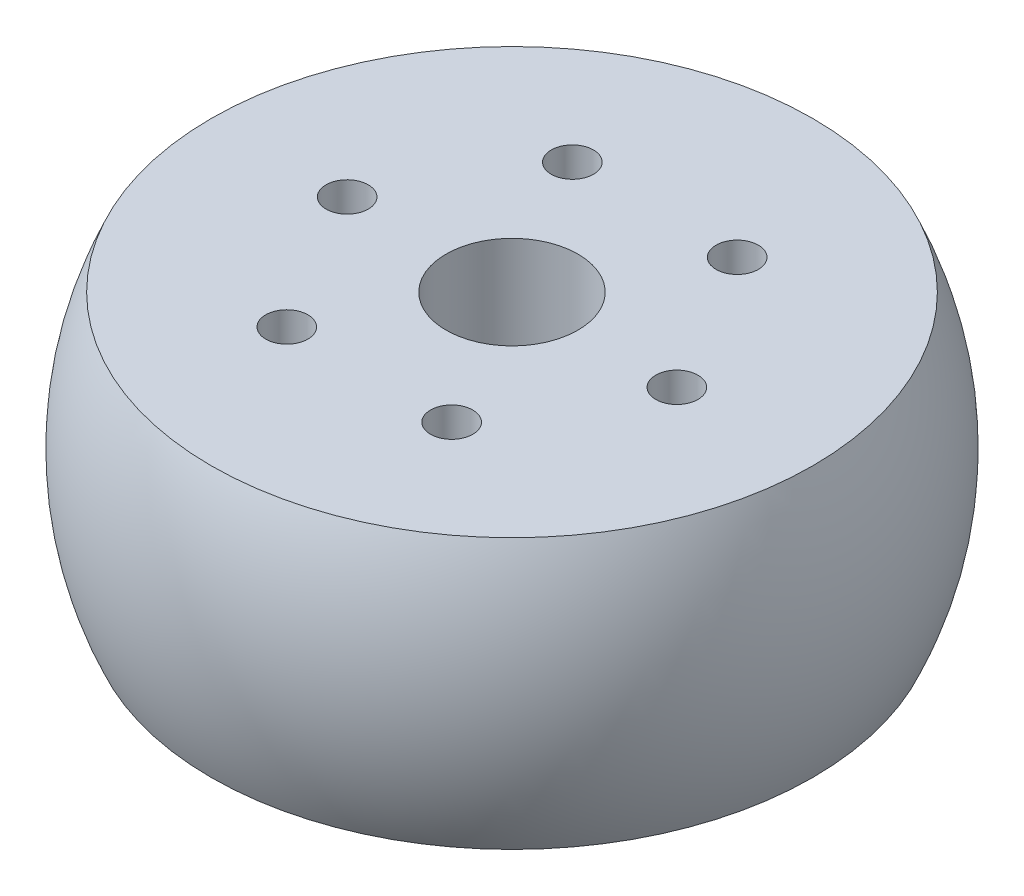
SolidWorks part; units mm, degrees
ref_plane "Front Plane" through (0, 0, 0) normal (0, 0, 1) x (1, 0, 0)
ref_plane "Top Plane" through (0, 0, 0) normal (0, 1, 0) x (1, 0, 0)
ref_plane "Right Plane" through (0, 0, 0) normal (1, 0, 0) x (0, 0, -1)
sketch "Sketch1" plane through (0, 0, 0) normal (1, 0, 0) x (0, 0, -1)
  line L0 (0, -6.5) -> (0, 6.5) construction
  line L1 (3.175, 6.5) -> (14.4833, 6.5)
  line L2 (3.175, 6.5) -> (3.175, -6.5)
  line L3 (3.175, -6.5) -> (14.4833, -6.5)
  line L4 (15.875, 0) -> (0, 0) construction
  circle A0 centre (0, 0) radius 15.875 construction
  arc A1 (14.4833, 6.5) -> (14.4833, -6.5) centre (0, 0) cw
  point P4 (0, 0)
  dimension "D1" = 6.35
  dimension "D2" = 13
  dimension "D3" = 15.875
revolve "Revolve1" add sketch "Sketch1" angle 360 about L0
sketch "Sketch3" plane through (0, 0, 0) normal (0, 1, 0) x (1, 0, 0)
  line L0 (0, 0) -> (7.9375, 0) construction
  circle A0 centre (7.9375, 0) radius 1.016
  dimension "D1" = 2.032
  dimension "D2" = 7.9375
extrude "Cut-Extrude1" cut sketch "Sketch3" against normal through all both and the other way through all
pattern_circular "CirPattern1" count 6 over 360 about axis through (0, -6.5, 0) along (0, -1, 0) of "Cut-Extrude1" reverse direction yes
